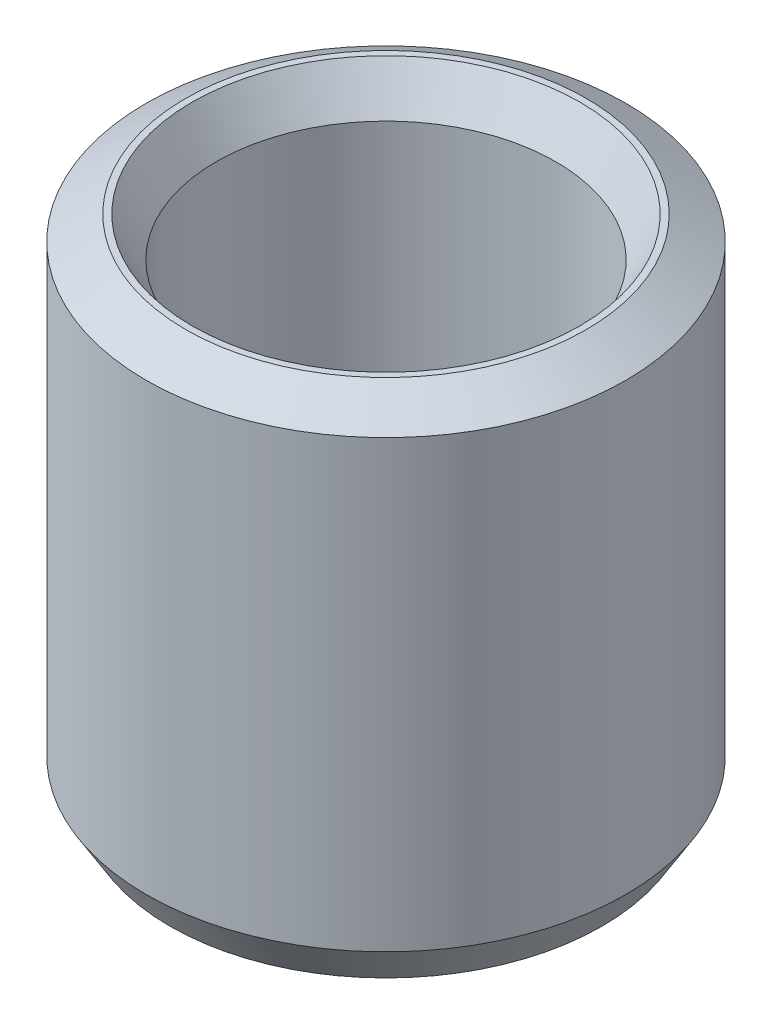
SolidWorks part; units mm, degrees
ref_plane "Front Plane" through (0, 0, 0) normal (0, 0, 1) x (1, 0, 0)
ref_plane "Top Plane" through (0, 0, 0) normal (0, 1, 0) x (1, 0, 0)
ref_plane "Right Plane" through (0, 0, 0) normal (1, 0, 0) x (0, 0, -1)
sketch "Sketch1" plane through (0, 0, 0) normal (0, 1, 0) x (1, 0, 0)
  circle A0 centre (0, 0) radius 35
  dimension "SLEEVE_OD" = 70
extrude "Boss-Extrude1" add sketch "Sketch1" along normal blind 74.2543
sketch "Sketch2" plane through (0, 0, 0) normal (0, 1, 0) x (1, 0, 0)
  circle A0 centre (0, 0) radius 24.7762
  dimension "BORE_D" = 49.5524
extrude "Cut-Extrude1" cut sketch "Sketch2" along normal through all
chamfer "Chamfer1" distance 3.5068 angle 58.754 4 edges at (0, 74.2543, 24.7762) (0, 0, 24.7762) (0, 0, 35) (0, 74.2543, 35) first distance on face at (0, 74.2543, 24.7762) first distance on face at (0, 0, 24.7762) first distance on face at (0, 74.2543, 35)
